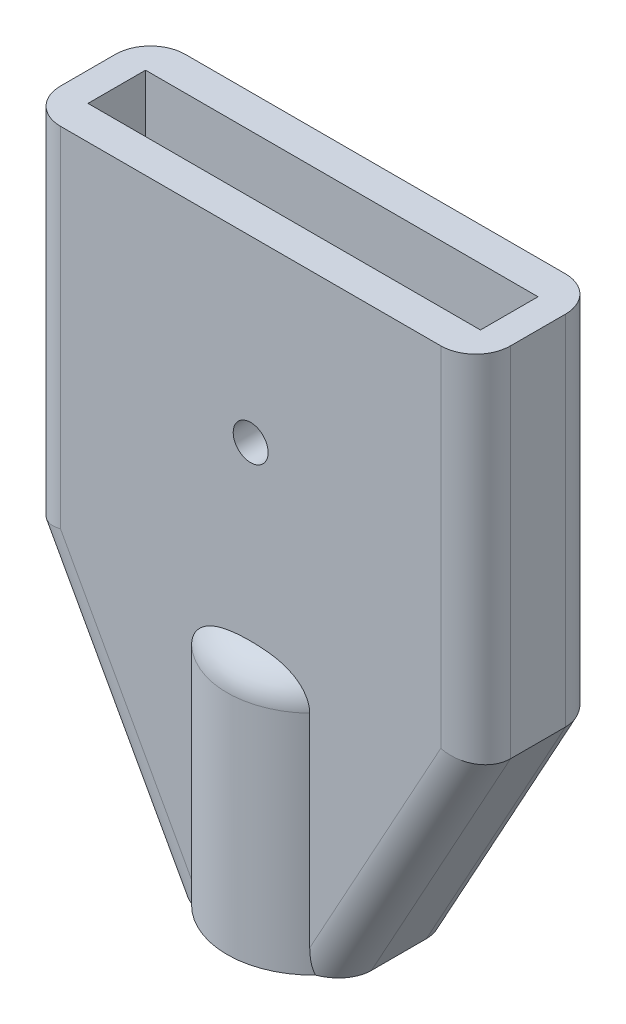
SolidWorks part; units mm, degrees
ref_plane "Front Plane" through (0, 0, 0) normal (0, 0, 1) x (1, 0, 0)
ref_plane "Top Plane" through (0, 0, 0) normal (0, 1, 0) x (1, 0, 0)
ref_plane "Right Plane" through (0, 0, 0) normal (1, 0, 0) x (0, 0, -1)
sketch "Sketch2" plane through (0, 0, 0) normal (0, 0, 1) x (1, 0, 0)
  line L0 (0, 0) -> (17.825, 0) construction
  line L1 (0, 0) -> (0, 51.1905) construction
  line L2 (12.9, 35) -> (12.9, 0) construction
  line L3 (7.975, 0) -> (17.825, 0)
  line L4 (0, 14.5) -> (0, 35)
  line L5 (0, 35) -> (25.8, 35)
  line L6 (25.8, 14.5) -> (25.8, 35)
  line L7 (0, 14.5) -> (25.8, 14.5) construction
  line L8 (7.975, 14.5) -> (7.975, 0) construction
  line L9 (17.825, 14.5) -> (17.825, 0) construction
  line L10 (17.825, 0) -> (25.8, 14.5)
  line L11 (0, 14.5) -> (7.975, 0)
  dimension "D1" = 25.8
  dimension "D2" = 35
  dimension "D3" = 14.5
  dimension "D4" = 4.925
  dimension "D5" = 4.925
  dimension "D6" = 9.85
extrude "Boss-Extrude1" add sketch "Sketch2" along normal blind 7.15
sketch "Sketch3" plane through (0, 0, 0) normal (0, -1, 0) x (1, 0, 0)
  line L0 (12.9, 7.15) -> (12.9, 0) construction
  line L1 (7.975, 7.15) -> (17.825, 7.15) construction
  line L2 (7.975, 0) -> (17.825, 0) construction
  line L3 (17.825, 3.575) -> (7.975, 3.575) construction
  line L4 (17.825, 7.15) -> (17.825, 0) construction
  line L5 (7.975, 7.15) -> (7.975, 0) construction
  circle A0 centre (12.9, 3.575) radius 4.925
  dimension "D1" = 9.85
extrude "Boss-Extrude2" add sketch "Sketch3" against normal blind 15
sketch "Sketch4" plane through (0, 0, 0) normal (0, -1, 0) x (1, 0, 0)
  line L0 (7.975, 3.575) -> (17.825, 3.575) construction
  line L1 (7.975, 7.15) -> (7.975, 0) construction
  line L2 (17.825, 7.15) -> (17.825, 0) construction
  line L3 (12.9, 3.575) -> (12.9, -1.35) construction
  line L4 (12.9, 3.575) -> (12.9, 8.5) construction
  arc A0 (9.5125, 0) -> (16.2875, 0) centre (12.9, 3.575) ccw construction
  arc A1 (16.2875, 7.15) -> (9.5125, 7.15) centre (12.9, 3.575) ccw construction
  circle A2 centre (12.9, 3.575) radius 2.925
  dimension "D1" = 5.85
extrude "Cut-Extrude1" cut sketch "Sketch4" against normal blind 13.5
sketch "Sketch5" plane through (0, 35, 0) normal (0, 1, 0) x (1, 0, 0)
  line L0 (0, -3.575) -> (25.8, -3.575) construction
  line L1 (0, -7.15) -> (0, 0) construction
  line L2 (25.8, -7.15) -> (25.8, 0) construction
  line L3 (12.9, 0) -> (12.9, -7.15) construction
  line L4 (16.2875, 0) -> (9.5125, 0) construction
  line L5 (25.8, -7.15) -> (0, -7.15) construction
  line L7 (1.65, -5.225) -> (24.15, -5.225)
  line L8 (1.65, -5.225) -> (1.65, -1.925)
  line L9 (1.65, -1.925) -> (24.15, -1.925)
  line L10 (24.15, -5.225) -> (24.15, -1.925)
  line L11 (1.65, -5.225) -> (24.15, -1.925) construction
  line L12 (1.65, -1.925) -> (24.15, -5.225) construction
  point P12 (12.9, -3.575)
  dimension "D1" = 3.3
  dimension "D2" = 22.5
extrude "Cut-Extrude2" cut sketch "Sketch5" against normal blind 18
sketch "Sketch6" plane through (0, 0, 0) normal (0, 0, -1) x (-1, 0, 0)
  line L0 (-25.8, 24.75) -> (0, 24.75) construction
  line L1 (-25.8, 14.5) -> (-25.8, 35) construction
  line L2 (0, 35) -> (0, 14.5) construction
  circle A0 centre (-12.9, 24.75) radius 1
  dimension "D1" = 2
extrude "Cut-Extrude3" cut sketch "Sketch6" against normal through all
fillet "Fillet1" radius 2 10 edges at (12.9, 15, 8.5) (12.9, 15, -1.35) (3.9875, 7.25, 7.15) (3.9875, 7.25, 0) (21.8125, 7.25, 7.15) (21.8125, 7.25, 0) (25.8, 24.75, 7.15) (0, 24.75, 7.15) (0, 24.75, 0) (25.8, 24.75, 0)
